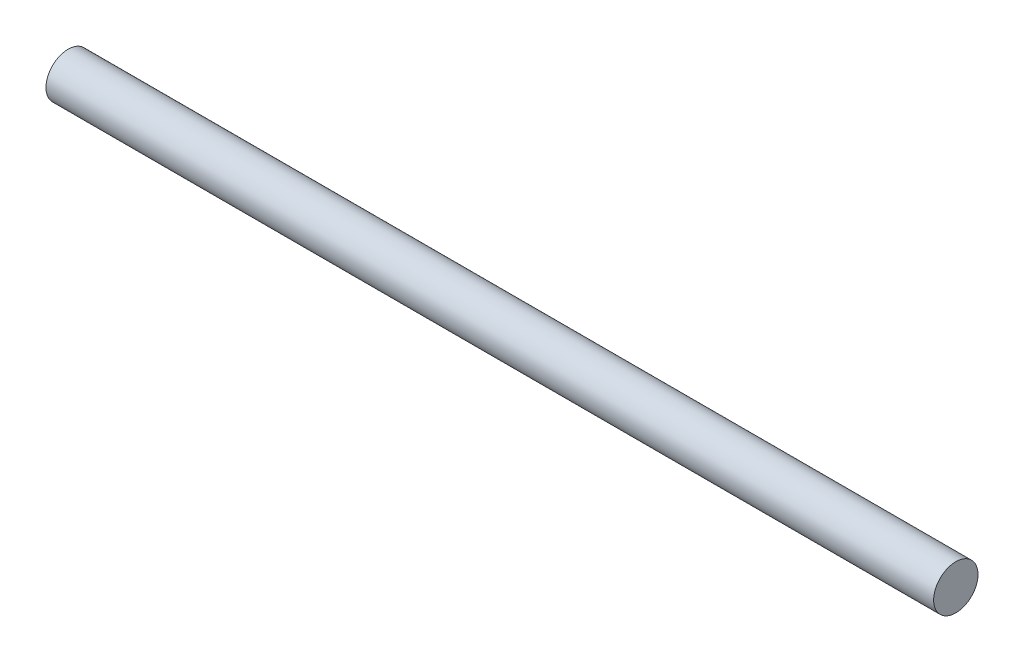
SolidWorks part; units mm, degrees
ref_plane "前视基准面" through (0, 0, 0) normal (0, 0, 1) x (1, 0, 0)
ref_plane "上视基准面" through (0, 0, 0) normal (0, 1, 0) x (1, 0, 0)
ref_plane "右视基准面" through (0, 0, 0) normal (1, 0, 0) x (0, 0, -1)
sketch "草图1" plane through (0, 0, 0) normal (1, 0, 0) x (0, 0, -1)
  circle A0 centre (0, 0) radius 1
  dimension "D1" = 2
extrude "凸台-拉伸1" add sketch "草图1" along normal blind 40
ref_axis "Axis1" through (-15.3184, 0, 0) along (1, 0, 0)
